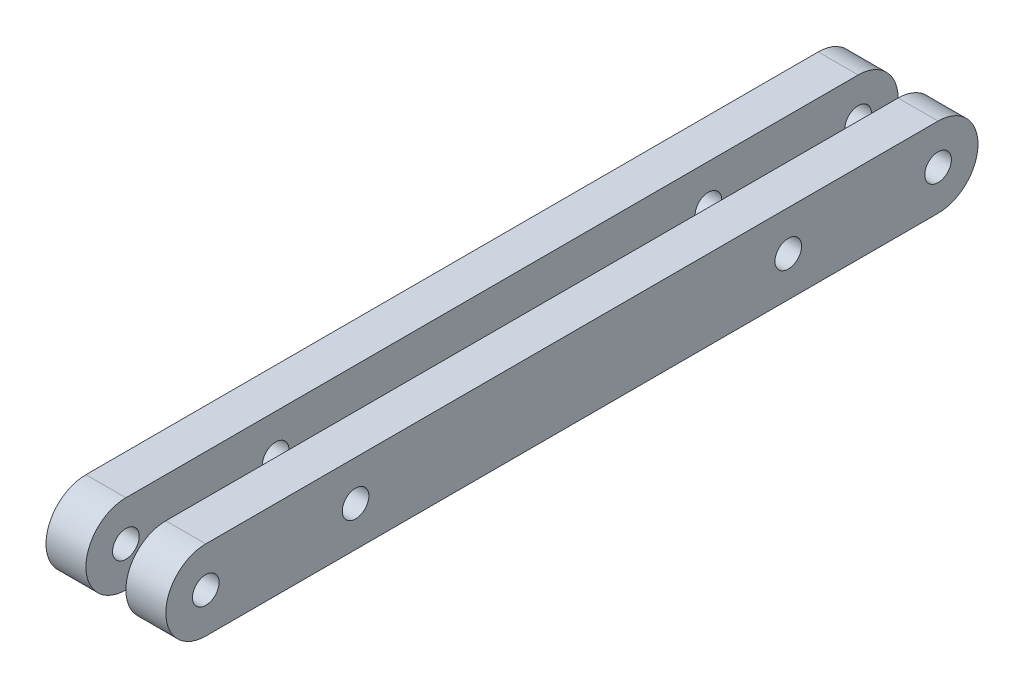
SolidWorks part; units mm, degrees
ref_plane "Front Plane" through (0, 0, 0) normal (0, 0, 1) x (1, 0, 0)
ref_plane "Top Plane" through (0, 0, 0) normal (0, 1, 0) x (1, 0, 0)
ref_plane "Right Plane" through (0, 0, 0) normal (1, 0, 0) x (0, 0, -1)
sketch "length (ref to equation file)" plane through (0, 0, 0) normal (1, 0, 0) x (0, 0, -1)
  line L0 (0, 0) -> (110, 0)
  dimension "D1" = 110
ref_axis "pivot w/ link 1" through (0, 0, 0) along (1, 0, 0)
ref_axis "pivot w/ platform" through (0, 0, -110) along (1, 0, 0)
ref_plane "Plane1" through (3, 0, 0) normal (1, 0, 0) x (0, 0, -1)
sketch "Sketch1" plane through (3, 0, 0) normal (1, 0, 0) x (0, 0, -1)
  line L0 (0, 0) -> (110, 0) construction
  line L1 (0, 6) -> (110, 6)
  line L2 (0, -6) -> (110, -6)
  arc A0 (0, 6) -> (0, -6) centre (0, 0) ccw
  arc A1 (110, -6) -> (110, 6) centre (110, 0) ccw
  point P4 (55, 0)
  dimension "D1" = 12
extrude "Boss-Extrude1" add sketch "Sketch1" along normal blind 6 contours L2 A1 L1 A0
sketch "Sketch2" plane through (9, 0, 0) normal (1, 0, 0) x (0, 0, -1)
  circle A0 centre (0, 0) radius 2
  circle A2 centre (110, 0) radius 2
  circle A5 centre (0, 0) radius 2 construction
extrude "Cut-Extrude1" cut sketch "Sketch2" against normal through all and the other way through all
mirror "Mirror4" about plane through (0, 0, 0) normal (1, 0, 0) of bodies 103
sketch "Sketch3" plane through (3, 0, 0) normal (1, 0, 0) x (0, 0, -1)
  line L0 (0, 0) -> (110, 0) construction
  line L1 (22.5, 0) -> (87.5, 0)
  line L2 (0, 6) -> (110, 6) construction
  line L3 (22.5, 6) -> (87.5, 6)
  line L4 (22.5, 6) -> (22.5, -6)
  line L5 (22.5, -6) -> (87.5, -6)
  line L6 (87.5, 6) -> (87.5, -6)
  line L7 (0, -6) -> (110, -6) construction
  point P5 (55, 0)
  point P7 (55, 0)
  line M14 (0, 6) -> (110, 6)
  line M16 (110, -6) -> (0, -6)
  dimension "D1" = 65
extrude "Boss-Extrude2" [suppressed] add sketch "Sketch3" against normal up to surface (6 mm away) contours L6 L4 M14 M16 up to face at (-3, 0, -2)
sketch "Sketch5" plane through (9, 0, 0) normal (1, 0, 0) x (0, 0, -1)
  point P0 (87.5, 0)
  point P2 (22.5, 0)
hole_wizard "Ø4.0mm Dowel Hole1" positions "Sketch5" profile "Sketch6" hole size "Ø4.0" standard "ANSI Metric" end condition through all
sketch "Sketch6" plane through (9, 0, -87.5) normal (0, 1, 0) x (0, 0, -1)
  line L0 (0, 0) -> (0, 18)
  line L1 (0, 18) -> (2, 18)
  line L2 (2, 18) -> (2, 0)
  line L5 (2, 0) -> (0, 0)
  line L11 (0, -6.35) -> (0, 107.95) construction
  dimension "Thru Hole Dia." = 4
  dimension "Thru Hole Depth" = 18
equation "\"link 2\"= 110mm"
equation "\"D1@length (ref to equation file)\" = \"link 2\""
equation "\"link 1 thickness\" = 6mm"
equation "\"beam width\" = 30mm"
equation "\"beam side wall thickness\" = 3mm"
equation "\"D1@Plane1\" = \"link 2 plane\""
equation "\"link 2 plane\"= \"link 1 thickness\" / 2"
equation "\"motor center z\" = 35mm"
equation "\"motor center y\" = 20mm"
equation "\"link 1\" = 40mm"
equation "\"pivot height\"= 140mm"
equation "\"beam length\" = 185mm"
equation "\"camera height\" = 250mm"
equation "\"link height\" = 12mm"
equation "\"D1@Sketch1\"=\"link height\""
equation "\"D1@Boss-Extrude1\"=\"link 1 thickness\""
